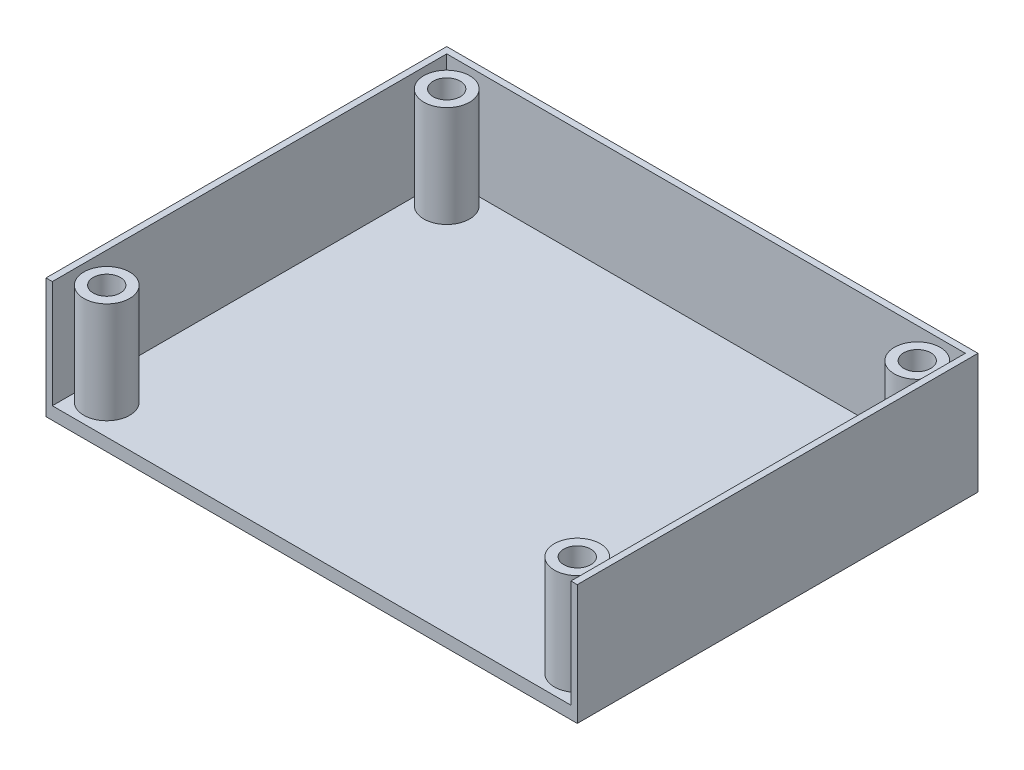
SolidWorks part; units mm, degrees
ref_plane "Front Plane" through (0, 0, 0) normal (0, 0, 1) x (1, 0, 0)
ref_plane "Top Plane" through (0, 0, 0) normal (0, 1, 0) x (1, 0, 0)
ref_plane "Right Plane" through (0, 0, 0) normal (1, 0, 0) x (0, 0, -1)
sketch "Sketch1" plane through (0, 0, 0) normal (0, 1, 0) x (1, 0, 0)
  line L0 (-66.8583, -50.2762) -> (-65.2708, -50.2762)
  line L1 (-65.2708, -50.2762) -> (64.8554, -50.2762)
  line L2 (-66.8583, -50.2762) -> (-66.8583, 50.2663)
  line L3 (-66.8583, 50.2663) -> (66.4429, 50.2663)
  line L4 (66.4429, -50.2762) -> (66.4429, 50.2663)
  line L5 (66.4429, -50.2762) -> (64.8554, -50.2762)
  line L8 (-65.2708, -50.2762) -> (-65.2708, 48.6788)
  line L9 (-65.2708, 48.6788) -> (64.8554, 48.6788)
  line L10 (64.8554, -50.2762) -> (64.8554, 48.6788)
  circle A0 centre (-59.2383, 42.6463) radius 3.4
  circle A1 centre (-59.2383, 42.6463) radius 5.75
  circle A2 centre (58.8229, 42.6463) radius 5.75
  circle A3 centre (58.8229, 42.6463) radius 3.4
  circle A4 centre (-59.2383, -42.6562) radius 5.75
  circle A5 centre (-59.2383, -42.6562) radius 3.4
  circle A6 centre (58.8229, -42.6562) radius 5.75
  circle A7 centre (58.8229, -42.6562) radius 3.4
  point P0 (0, 0)
  dimension "D5" = 7.62
  dimension "D7" = 7.62
  dimension "D1" = 133.3013
  dimension "D2" = 100.5425
  dimension "D3" = 1.5875
  dimension "D4" = 1.5875
  dimension "D6" = 7.62
  dimension "D8" = 7.62
  dimension "D9" = 7.62
  dimension "D10" = 7.62
  dimension "D11" = 7.62
  dimension "D12" = 7.62
  dimension "D13" = 1.5875
extrude "Boss-Extrude12" add sketch "Sketch1" along normal blind 3.175 contours L0 L1 L5 L4 L3 L2
extrude "Boss-Extrude13" add sketch "Sketch1<23>" along normal blind 30.1625 contours L10 L5 L4 L3 L2 L0 L8 L9 region at (-66.6913, 0, 0.005)
sketch "Sketch1<23>" plane through (0, 0, 0) normal (0, 1, 0) x (1, 0, 0) same geometry as "Sketch1"
extrude "Boss-Extrude15" add sketch "Sketch1<25>" along normal blind 28.575 contours A1 A0 | A2 A3 | A6 A7 | A4 A5 region at (-64.8257, 0, -42.6463) region at (53.2356, 0, -42.6463) region at (-64.8257, 0, 42.6562) region at (53.2356, 0, 42.6562)
sketch "Sketch1<25>" plane through (0, 0, 0) normal (0, 1, 0) x (1, 0, 0) same geometry as "Sketch1"
extrude "Cut-Extrude3" cut sketch "Sketch1<27>" along normal blind 28.575 contours A5 | A5 | A0 | A3 | A7 region at (-59.2383, 0, 42.6562)
sketch "Sketch1<27>" plane through (0, 0, 0) normal (0, 1, 0) x (1, 0, 0) same geometry as "Sketch1"
chamfer "Chamfer2" distance 1.45 angle 45 4 edges at (58.8229, 0, 46.0562) (58.8229, 0, -39.2463) (-59.2383, 0, 46.0562) (-59.2383, 0, -39.2463)
